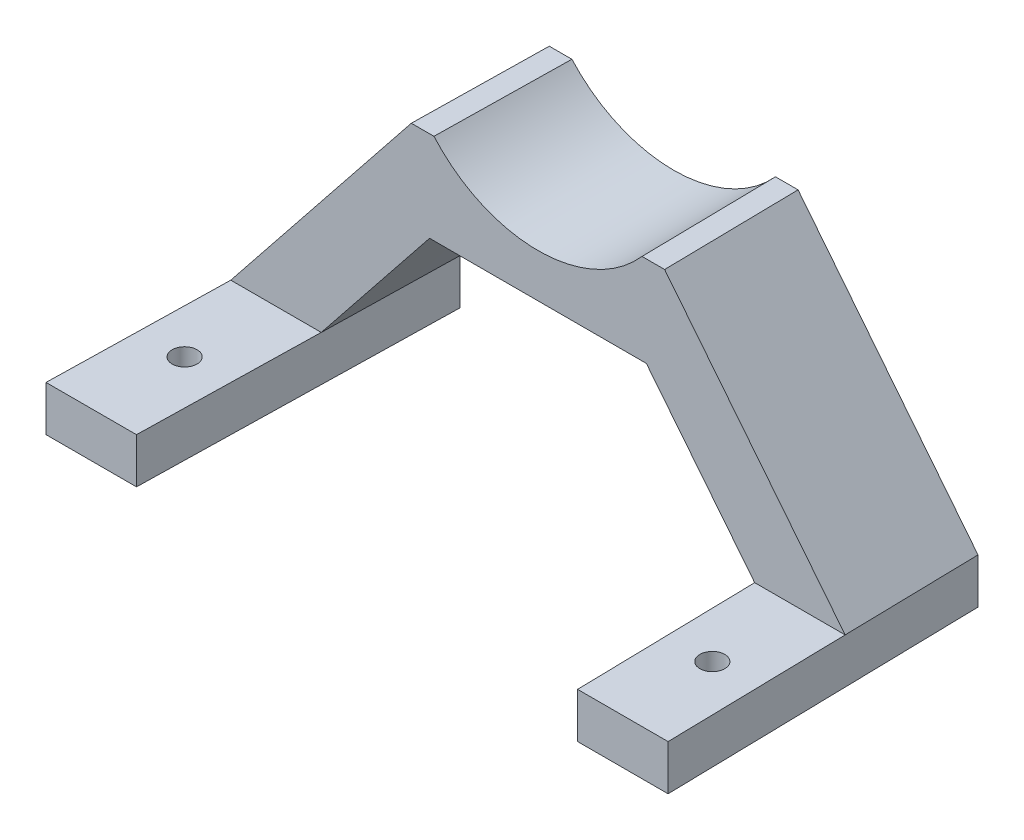
SolidWorks part; units mm, degrees
ref_plane "Front Plane" through (0, 0, 0) normal (0, 0, 1) x (1, 0, 0)
ref_plane "Top Plane" through (0, 0, 0) normal (0, 1, 0) x (1, 0, 0)
ref_plane "Right Plane" through (0, 0, 0) normal (1, 0, 0) x (0, 0, -1)
sketch "Sketch1" plane through (0, 0, 0) normal (0, 1, 0) x (1, 0, 0)
  line L0 (0, 0) -> (20.0045, 0)
  line L1 (20.0045, 0) -> (21.4891, 70)
  line L2 (21.4891, 70) -> (1.4846, 70)
  line L3 (1.4846, 70) -> (0, 0)
  line L4 (68.7637, 0) -> (68.7637, 140) construction
  line L5 (21.4891, 70) -> (22.9737, 140) construction
  line L6 (116.0384, 70) -> (136.0429, 70)
  line L7 (117.523, 0) -> (116.0384, 70)
  line L8 (137.5275, 0) -> (117.523, 0)
  line L9 (136.0429, 70) -> (137.5275, 0)
  line L10 (0.4332, 20.4241) -> (20.4287, 20) construction
  circle A0 centre (10.4309, 20.212) radius 2.75
  circle A2 centre (127.0966, 20.212) radius 2.75
  dimension "D6" = 5.5
  dimension "D1" = 1.215
  dimension "D2" = 45.79
  dimension "D3" = 20
  dimension "D4" = 70
  dimension "D5" = 140
  dimension "D7" = 20
extrude "Boss-Extrude1" add sketch "Sketch1" along normal blind 10
sketch "Sketch2" plane through (0, 0, -70) normal (0, 0, -1) x (-1, 0, 0)
  line L0 (-21.4891, 10) -> (-1.4846, 10) construction
  line L1 (-116.0384, 10) -> (-21.4891, 10) construction
  line L2 (-68.7637, 10) -> (-68.7637, 50) construction
  line L3 (-91.2637, 60.005) -> (-96.2637, 60.005)
  line L4 (-46.2637, 60.005) -> (-41.2637, 60.005)
  line L5 (-92.1733, 40) -> (-45.3542, 40)
  line L6 (-45.3542, 40) -> (-21.4891, 10)
  line L7 (-92.1733, 40) -> (-116.0384, 10)
  line L8 (-116.0384, 10) -> (-136.0429, 10)
  line L9 (-136.0429, 10) -> (-96.2637, 60.005)
  line L10 (-41.2637, 60.005) -> (-1.4846, 10)
  line L11 (-1.4846, 10) -> (-21.4891, 10)
  arc A0 (-91.2637, 60.005) -> (-46.2637, 60.005) centre (-68.7637, 80.3024) ccw
  point P3 (-68.7637, 50)
  dimension "D5" = 45
  dimension "D1" = 40
  dimension "D2" = 5
  dimension "D3" = 10
  dimension "D4" = 20
ref_plane "Plane1" through (0, 0, -40) normal (0, 0, -1) x (-1, 0, 0)
sketch "Sketch3" plane through (0, 0, -40) normal (0, 0, -1) x (-1, 0, 0)
  line L0 (-136.6791, 10) -> (-96.7637, 60.005)
  line L1 (-96.7637, 60.005) -> (-91.7637, 60.005)
  line L2 (-92.7278, 40) -> (-44.7997, 40)
  line L3 (-68.7637, 10) -> (-68.7637, 50) construction
  line L4 (-68.7637, 10) -> (-68.7637, 50) construction
  line L5 (-45.7637, 60.005) -> (-40.7637, 60.005)
  line L6 (-40.7637, 60.005) -> (-0.8484, 10)
  line L7 (-0.8484, 10) -> (-20.8529, 10)
  line L8 (-20.8529, 10) -> (-44.7997, 40)
  line L9 (-92.7278, 40) -> (-116.6746, 10)
  line L10 (-116.6746, 10) -> (-136.6791, 10)
  line L11 (-92.1733, 40) -> (-45.3542, 40) construction
  line L19 (-91.2637, 60.005) -> (-96.2637, 60.005) construction
  arc A0 (-91.7637, 60.005) -> (-45.7637, 60.005) centre (-68.7637, 80.3024) ccw
  point P26 (-68.7637, 49.6269)
  dimension "D1" = 5
  dimension "D2" = 46
loft "Loft1" add profiles "Sketch2", "Sketch3" connector at (46.2637, 60.005, -70) connector at (45.7637, 60.005, -40)
